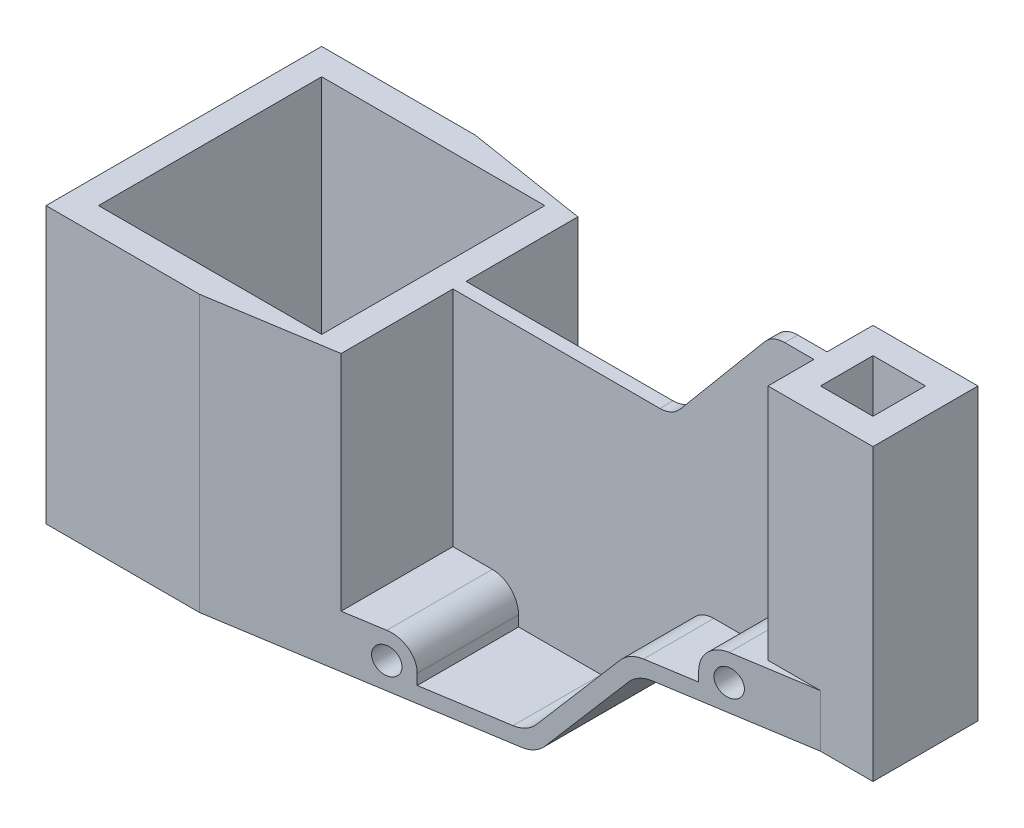
SolidWorks part; units mm, degrees
material "Alliage 1060"
ref_plane "Plan de face" through (0, 0, 0) normal (0, 0, 1) x (1, 0, 0)
ref_plane "Plan de dessus" through (0, 0, 0) normal (0, 1, 0) x (1, 0, 0)
ref_plane "Plan de droite" through (0, 0, 0) normal (1, 0, 0) x (0, 0, -1)
sketch "Esquisse1" plane through (0, 0, 0) normal (0, 0, 1) x (1, 0, 0)
  line L0 (52.5, 20) -> (67.5, 20)
  line L2 (0, 0) -> (0, 105)
  line L4 (-52.5, 0) -> (-52.5, 105)
  line L6 (0, 0) -> (0, 105)
  line L8 (52.5, 0) -> (52.5, 105)
  line L12 (230, 40) -> (230, 150.5)
  line L13 (77.5, 10) -> (77.5, 6)
  line L14 (77.5, 6) -> (108.9751, 6)
  line L15 (116.6355, 9.5721) -> (144.2048, 42.4279)
  line L16 (151.8652, 46) -> (170, 46)
  line L17 (170, 46) -> (170, 50)
  line L18 (180, 60) -> (210, 60)
  line L19 (210, 40) -> (210, 150.5)
  line L20 (154.6631, 40) -> (230, 40)
  line L21 (119.4334, 3.5721) -> (147.0026, 36.4279)
  line L22 (-52.5, 105) -> (131.3445, 105)
  line L23 (139.005, 108.5721) -> (171.1893, 146.9279)
  line L24 (178.8497, 150.5) -> (230, 150.5)
  line L25 (-52.5, 0) -> (96.6819, 0)
  line L26 (190, 60) -> (190, 150.5)
  line L27 (0, 105) -> (0, 150.5)
  line L28 (0, 150.5) -> (178.8497, 150.5)
  line L29 (96.6819, 0) -> (230, 0)
  line L30 (230, 0) -> (230, 40)
  circle A0 centre (67.5, 10) radius 5
  circle A1 centre (180, 50) radius 5
  arc A2 (170, 50) -> (180, 60) centre (180, 50) cw
  arc A3 (67.5, 20) -> (77.5, 10) centre (67.5, 10) cw
  arc A6 (144.2048, 42.4279) -> (151.8652, 46) centre (151.8652, 36) cw
  arc A7 (108.9751, 6) -> (116.6355, 9.5721) centre (108.9751, 16) ccw
  arc A9 (171.1893, 146.9279) -> (178.8497, 150.5) centre (178.8497, 140.5) cw
  arc A10 (131.3445, 105) -> (139.005, 108.5721) centre (131.3445, 115) ccw
  arc A11 (111.7729, 0) -> (119.4334, 3.5721) centre (111.7729, 10) ccw
  arc A12 (147.0026, 36.4279) -> (154.6631, 40) centre (154.6631, 30) cw
  point P48 (150, 40)
  dimension "D14" = 10
  dimension "D15" = 10
  dimension "D16" = 10
  dimension "D8" = 10
  dimension "D20" = 10
  dimension "D17" = 10
  dimension "D29" = 10
  dimension "D30" = 10
  dimension "B" = 105
  dimension "D2" = 10
  dimension "Z" = 120
  dimension "D6" = 130
  dimension "D7" = 6
  dimension "D12" = 10
  dimension "D13" = 10
  dimension "D19" = 50
  dimension "A" = 210
  dimension "X" = 52.5
  dimension "Y" = 110.5
  dimension "D21" = 105
  dimension "D22" = 20
  dimension "D3" = 52.5
  dimension "D4" = 20
  dimension "D11" = 10
  dimension "D23" = 6
  dimension "D24" = 6
  dimension "D25" = 40
  dimension "D27" = 20
  dimension "D28" = 60
  dimension "D26" = 40
extrude "Boss.-Extru.1" add sketch "Esquisse1" along normal mid plane 105 contours L4 L25 L2 L22 region at (-26.25, 52.5, 0)
sketch "Esquisse2" plane through (0, 105, 0) normal (0, 1, 0) x (1, 0, 0)
  line L0 (0, 52.5) -> (6, 52.5)
  line L1 (6, 52.5) -> (210, 20)
  line L2 (0, -52.5) -> (0, 52.5) construction
  line L3 (190, -20) -> (230, -20)
  line L4 (-56.1426, 0) -> (227.5047, 0) construction
  line L5 (190, -20) -> (190, 20)
  line L6 (190, 20) -> (230, 20)
  line L7 (230, -20) -> (230, 20)
  line L8 (190, -20) -> (230, 20) construction
  line L9 (190, 20) -> (230, -20) construction
  line L10 (200, 10) -> (220, 10)
  line L11 (220, -10) -> (220, 10)
  line L12 (200, -10) -> (220, -10)
  line L13 (200, -10) -> (200, 10)
  line L14 (-42.5, 42.5) -> (-42.5, -42.5)
  line L15 (-52.5, 52.5) -> (6, 52.5)
  line L18 (52.5, 45.0919) -> (52.5, -45.0919)
  line L19 (-42.5, -42.5) -> (42.5, -42.5)
  line L20 (42.5, 42.5) -> (42.5, -42.5)
  line L21 (-42.5, 42.5) -> (42.5, 42.5)
  line L22 (-52.5, -52.5) -> (-52.5, 52.5) construction
  line L23 (-52.5, 52.5) -> (52.5, 52.5) construction
  line L24 (52.5, 52.5) -> (52.5, -52.5) construction
  line L25 (-52.5, -52.5) -> (52.5, -52.5) construction
  line L26 (-52.5, 52.5) -> (-52.5, -52.5) construction
  line L27 (6, -52.5) -> (210, -20)
  line L28 (0, -52.5) -> (6, -52.5)
  line L29 (0, 52.5) -> (0, 42.5)
  line L30 (0, -42.5) -> (0, -52.5)
  line L31 (-52.5, -52.5) -> (0, -52.5) construction
  point P5 (210, 0)
  line M20 (0, -52.5) -> (0, 52.5)
  dimension "D8" = 10
  dimension "D1" = 210
  dimension "D2" = 6
  dimension "D3" = 40
  dimension "D4" = 40
  dimension "D6" = 10
  dimension "D7" = 10
  dimension "D9" = 10
  dimension "D10" = 105
  dimension "D5" = 10
extrude "Boss.-Extru.2" add sketch "Esquisse2" against normal blind 105 and the other way blind 45.5 contours L18 L27 L3 L5 L6 L1 | L28 L27 L18 L1 L0 L21 L20 L19 M20 | L3 L7 L6 L5 L12 L13 L10 L11 region at (3, 105, -51.3261) region at (114.4557, 105, 0) region at (220, 105, -19.4343)
extrude "Enlèv. mat.-Extru.1" cut sketch "Esquisse2<3>" against normal through all contours L21 L14 L19 M20 | L21 L19 L20 M20 region at (-21.25, 105, 0) region at (21.25, 105, 0)
sketch "Esquisse2<3>" plane through (0, 105, 0) normal (0, 1, 0) x (1, 0, 0) same geometry as "Esquisse2"
extrude "Enlèv. mat.-Extru.3" cut sketch "Esquisse1<4>" against normal through all from offset 2.5 contours A9 L23 A10 L22 L8 L0 A3 L13 L14 A7 L15 A6 L16 L17 A2 L18 L26 L24 region at (120.5192, 71.6671, 0) offset against normal yes
sketch "Esquisse1<4>" plane through (0, 0, 0) normal (0, 0, 1) x (1, 0, 0) same geometry as "Esquisse1"
extrude "Enlèv. mat.-Extru.4" cut sketch "Esquisse1<5>" along normal through all from offset 2.5 contours A9 L23 A10 L22 L8 L0 A3 L13 L14 A7 L15 A6 L16 L17 A2 L18 L26 L24 region at (120.5192, 71.6671, 0)
sketch "Esquisse1<5>" plane through (0, 0, 0) normal (0, 0, 1) x (1, 0, 0) same geometry as "Esquisse1"
extrude "Enlèv. mat.-Extru.5" cut sketch "Esquisse1<6>" against normal through all both and the other way through all contours L23 A9 L28 L27 L22 A10 | L21 L29 L30 L20 | A0 | A1 region at (77.9567, 128.7021, 0) region at (181.0975, 18.8142, 0)
sketch "Esquisse1<6>" plane through (0, 0, 0) normal (0, 0, 1) x (1, 0, 0) same geometry as "Esquisse1"
extrude "Enlèv. mat.-Extru.6" cut sketch "Esquisse1<7>" against normal blind 32.5 from offset 20 contours L26 L18 L19 L24 region at (200, 105.25, 0) offset against normal yes
sketch "Esquisse1<7>" plane through (0, 0, 0) normal (0, 0, 1) x (1, 0, 0) same geometry as "Esquisse1"
extrude "Enlèv. mat.-Extru.7" cut sketch "Esquisse1<8>" along normal blind 32.5 from offset 20 contours L26 L18 L19 L24 region at (200, 105.25, 0)
sketch "Esquisse1<8>" plane through (0, 0, 0) normal (0, 0, 1) x (1, 0, 0) same geometry as "Esquisse1"
equation "\"D3@Esquisse1\"=\"B@Esquisse1\"/2"
equation "\"Z@Esquisse1\" = \"B@Esquisse1\" + 15"
equation "\"D21@Esquisse1\"=\"B@Esquisse1\""
equation "\"Y@Esquisse1\" = \"B@Esquisse1\" + 5.5"
equation "\"X@Esquisse1\" = \"A@Esquisse1\" / 4"
equation "\"D10@Esquisse2\"=\"B@Esquisse1\""
equation "\"D1@Esquisse2\"=\"A@Esquisse1\""
equation "\"D1@Boss.-Extru.1\"=\"A@Esquisse1\"/2"
equation "\"D1@Boss.-Extru.2\"=\"D10@Esquisse2\""
equation "\"D1@Enlèv. mat.-Extru.6\"=(\"A@Esquisse1\"/2-\"D26@Esquisse1\")/2"
equation "\"D1@Enlèv. mat.-Extru.7\"=(\"A@Esquisse1\"/2-\"D26@Esquisse1\")/2"
equation "\"A\" = 210"
equation "\"B\" = 105"
